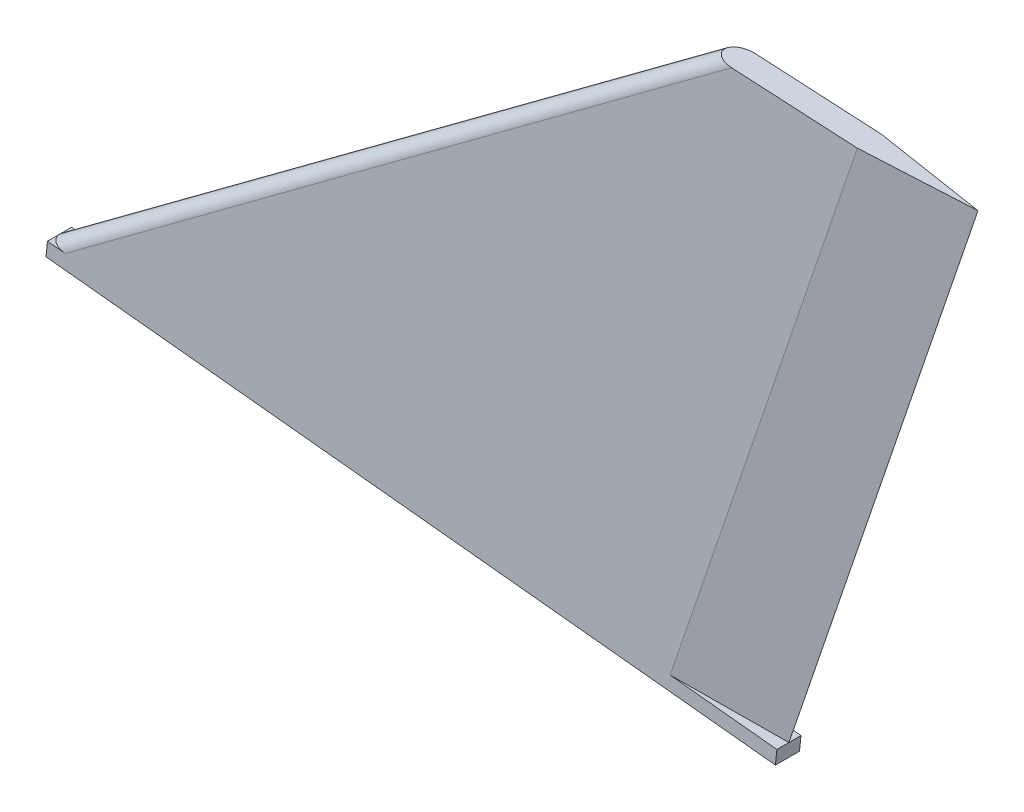
SolidWorks part; units mm, degrees
ref_plane "Front Plane" through (0, 0, 0) normal (0, 0, 1) x (1, 0, 0)
ref_plane "Top Plane" through (0, 0, 0) normal (0, 1, 0) x (1, 0, 0)
ref_plane "Right Plane" through (0, 0, 0) normal (1, 0, 0) x (0, 0, -1)
sketch "Sketch1" plane through (0, 0, 0) normal (0, 0, 1) x (1, 0, 0)
  line L0 (0, 0) -> (254.3409, -26.3284)
  line L1 (-15.1322, -12.3428) -> (27.7903, -12.3428)
  line L2 (0, 0) -> (231.9955, 171.9987)
  line L3 (231.9955, 171.9987) -> (320.268, 167.2532)
  line L4 (320.268, 167.2532) -> (254.3409, -26.3284)
  dimension "D1" = 5.91
  dimension "D2" = 255.7
  dimension "D3" = 204.5
  dimension "D4" = 88.4
  dimension "D5" = 288.8
  dimension "D6" = 140.37
extrude "Boss-Extrude1" add sketch "Sketch1" along normal blind 8.4 contours L4 L3 L2 L0 region at (189.7329, 62.9811, 0)
ref_plane "Plane1" through (84.3261, 247.6067, 0) normal (-0.3224, -0.9466, 0) x (0, 0, -1)
sketch "Sketch4" plane through (84.3261, 247.6067, 0) normal (-0.3224, -0.9466, 0) x (0, 0, -1)
  line L0 (0, 212.7494) -> (-4.2, 249.2494)
  line L1 (0, 164.1599) -> (0, 249.2494) construction
  line L2 (-8.4, 249.2494) -> (0, 249.2494) construction
  line L3 (-4.2, 249.2494) -> (0, 249.2494)
  line L4 (0, 249.2494) -> (0, 212.7494)
  dimension "D1" = 36.5
extrude "Cut-Extrude2" cut sketch "Sketch4" along normal through all
sketch "Sketch10" plane through (84.3261, 247.6067, 0) normal (-0.3224, -0.9466, 0) x (0, 0, -1)
  line L0 (-4.2, 249.2494) -> (-8.4, 212.7494)
  line L1 (-8.4, 212.7494) -> (-8.4, 249.2494)
  line L2 (-8.4, 249.2494) -> (-4.2, 249.2494) construction
  line L3 (-8.4, 249.2494) -> (-4.2, 249.2494)
  dimension "D1" = 36.5
extrude "Cut-Extrude4" cut sketch "Sketch10" along normal through all
fillet "Fillet1" radius 4.2 2 edges at (115.9977, 85.9993, 0) (115.9977, 85.9993, 8.4)
sketch "Sketch14" plane through (0, 0, 0) normal (-0.103, -0.9947, 0) x (0.9947, -0.103, 0)
  line L1 (0, 0) -> (255.7, 0)
  line L2 (0, 0) -> (0, 8.4)
  line L3 (0, 8.4) -> (255.7, 8.4)
  line L4 (255.7, 0) -> (255.7, 8.4)
extrude "Boss-Extrude2" add sketch "Sketch14" along normal blind 5
